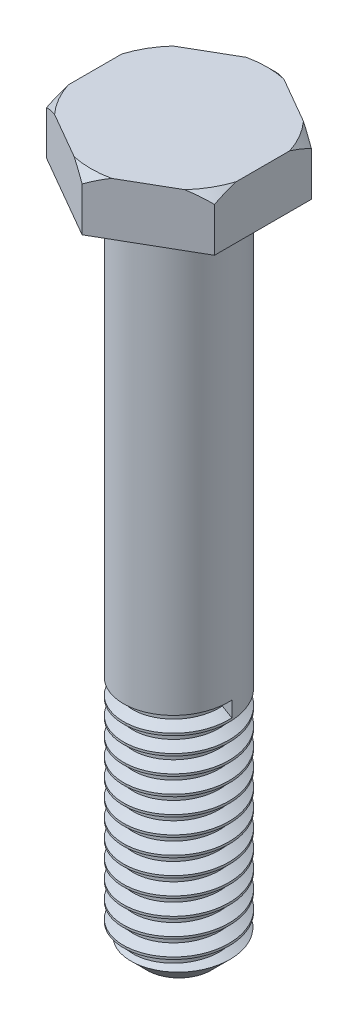
SolidWorks part; units mm, degrees
ref_plane "Front Plane" through (0, 0, 0) normal (0, 0, 1) x (1, 0, 0)
ref_plane "Top Plane" through (0, 0, 0) normal (0, 1, 0) x (1, 0, 0)
ref_plane "Right Plane" through (0, 0, 0) normal (1, 0, 0) x (0, 0, -1)
sketch "Sketch1" plane through (0, 0, 0) normal (0, 0, 1) x (1, 0, 0)
  line L0 (-3, 38) -> (-5.5, 38)
  line L1 (0, 0) -> (-3, 0)
  line L4 (-3, 0) -> (-3, 38)
  line L5 (0, 0) -> (-3, 38) construction
  line L6 (0, 0) -> (-3, 0) construction
  line L7 (-5.5, 38) -> (-5.5, 41)
  line L8 (-5.5, 41) -> (0, 41)
  line L9 (0, -55) -> (0, 55) construction
  line L10 (0, 41) -> (0, 0)
  line L11 (0, 41.7304) -> (0, -34.6539) construction
  line L12 (55, 0) -> (-55, 0) construction
  point P0 (0, 0)
  dimension "D1" = 3
  dimension "D2" = 5.5
  dimension "D3" = 0
  dimension "D4" = 41
revolve "Revolve1" add sketch "Sketch1" angle 360 about L11
sketch "Sketch2" plane through (0, 41, 0) normal (0, 1, 0) x (1, 0, 0)
  line L1 (4.7631, -2.75) -> (4.7631, 2.75)
  line L2 (4.7631, 2.75) -> (0, 5.5)
  line L3 (0, 5.5) -> (-4.7631, 2.75)
  line L4 (-4.7631, 2.75) -> (-4.7631, -2.75)
  line L5 (-4.7631, -2.75) -> (0, -5.5)
  line L6 (0, -5.5) -> (4.7631, -2.75)
  circle A0 centre (0, 0) radius 4.7631 construction
  circle A1 centre (0, 0) radius 5.5 construction
  dimension "D1" = 5.5
extrude "Cut-Extrude1" cut sketch "Sketch2" against normal blind 10 flip side to cut
sketch "Sketch3" plane through (0, 0, 0) normal (1, 0, 0) x (0, 0, -1)
  line L0 (-5, 41) -> (-5.5, 40.5)
  line L1 (-2.75, 41) -> (-5.5, 41) construction
  line L2 (-5.5, 38) -> (-5.5, 41) construction
  line L3 (-5, 41) -> (-5.5, 41)
  line L4 (-5.5, 41) -> (-5.5, 40.5)
  line L5 (0, 43.5087) -> (0, -6.9279) construction
  line L6 (0, 5.2395) -> (0, -5.2395) construction
  dimension "D1" = 0.5
  dimension "D2" = 0.5
revolve "Cut-Revolve1" cut sketch "Sketch3" angle 360 about L5
thread "Thread2" pitch 1 method cut profile "Thread Profile2" start angle 0, offset 0, length 13, pitch 1, diameter 6
ref_plane "Plane2" through (3, 0, 0) normal (0, 0, 1) x (1, 0, 0)
sketch "Thread Profile2" plane through (3, 0, 0) normal (0, 0, 1) x (1, 0, 0)
  line L0 (0, 0) -> (0, 1) construction
  line L11 (0, 0) -> (0, 0.875)
  line L12 (0, 0.875) -> (-0.5413, 0.5625)
  line L13 (-0.5413, 0.5625) -> (-0.5413, 0.3125)
  line L15 (-0.5413, 0.3125) -> (0, 0)
  line L17 (-0.5413, 0.4375) -> (0, 0.4375) construction
  point P2 (0, 0)
  dimension "Pitch" = 1
  dimension "Profile_Angle" = 60
  dimension "Profile_Land" = 0.25
  dimension "Profile_Height" = 0.5413
sketch "Sketch18" plane through (0, 0, 0) normal (1, 0, 0) x (0, 0, -1)
  line L0 (3.3118, 1.4904) -> (1.5145, -0.3015)
  line L1 (1.5145, -0.3015) -> (3.4682, -0.3015)
  line L2 (3.4682, -0.3015) -> (3.3118, 1.4904)
  line L3 (0, -0.5861) -> (0, 2.6068) construction
  line L4 (0, 5.2395) -> (0, -5.2395) construction
revolve "Cut-Revolve3" cut sketch "Sketch18" angle 360 about L3
